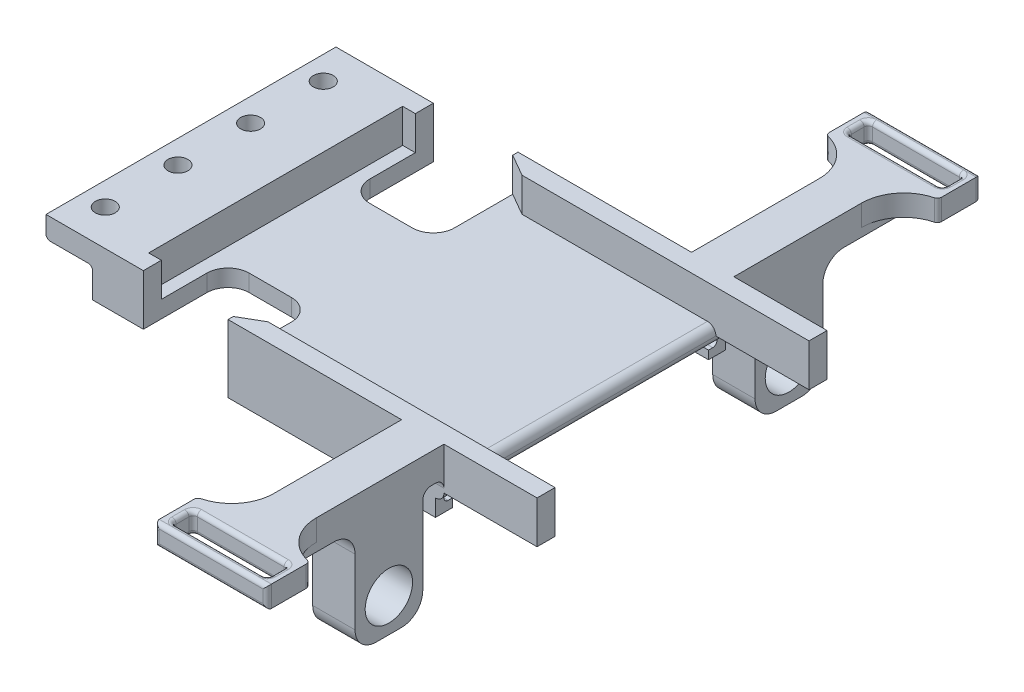
SolidWorks part; units mm, degrees
ref_plane "Front Plane" through (0, 0, 0) normal (0, 0, 1) x (1, 0, 0)
ref_plane "Top Plane" through (0, 0, 0) normal (0, 1, 0) x (1, 0, 0)
ref_plane "Right Plane" through (0, 0, 0) normal (1, 0, 0) x (0, 0, -1)
sketch "Sketch1" plane through (0, 0, 0) normal (0, 1, 0) x (1, 0, 0)
  line L1 (-62.4681, 12.4877) -> (31.5319, 12.4877)
  line L2 (-62.4681, 12.4877) -> (-62.4681, -56.0123)
  line L3 (-62.4681, -56.0123) -> (31.5319, -56.0123)
  line L4 (31.5319, 12.4877) -> (31.5319, -56.0123)
  dimension "D1" = 94
  dimension "D2" = 68.5
extrude "Boss-Extrude1" add sketch "Sketch1" along normal blind 12
sketch "Sketch3" plane through (0, 0, 56.0123) normal (0, 0, 1) x (1, 0, 0)
  line L0 (-62.4681, 12) -> (-62.4681, 0) construction
  line L1 (-62.4681, -3) -> (-51.4681, -3)
  line L2 (-62.4681, -3) -> (-62.4681, 7)
  line L3 (-62.4681, 7) -> (-51.4681, 7)
  line L4 (-51.4681, -3) -> (-51.4681, 7)
  line L5 (-62.4681, 12) -> (31.5319, 12) construction
  dimension "D1" = 11
  dimension "D2" = 10
  dimension "D3" = 5
extrude "Cut-Extrude1" cut sketch "Sketch3" against normal up to next
sketch "Sketch4" plane through (31.5319, 0, 0) normal (1, 0, 0) x (0, 0, -1)
  line L0 (-56.0123, 12) -> (12.4877, 12) construction
  line L1 (-51.7623, 12) -> (8.2377, 12)
  line L2 (-51.7623, 12) -> (-51.7623, 4)
  line L3 (-51.7623, 4) -> (8.2377, 4)
  line L4 (8.2377, 12) -> (8.2377, 4)
  line L5 (-56.0123, 12) -> (-56.0123, 0) construction
  dimension "D1" = 8
  dimension "D2" = 4.25
  dimension "D3" = 60
extrude "Cut-Extrude2" cut sketch "Sketch4" against normal blind 74
sketch "Sketch5" plane through (0, 7, 0) normal (0, -1, 0) x (1, 0, 0)
  line L0 (-56.9681, 56.0123) -> (-56.9681, -14.253) construction
  line L1 (-51.4681, 56.0123) -> (-62.4681, 56.0123) construction
  line L2 (-62.4681, -12.4877) -> (-51.4681, -12.4877) construction
  circle A0 centre (-56.9681, 47.5123) radius 2.35
  circle A1 centre (-56.9681, 30.3456) radius 2.35
  circle A2 centre (-56.9681, 13.179) radius 2.35
  circle A3 centre (-56.9681, -3.9877) radius 2.35
  dimension "D1" = 4.7
  dimension "D4" = 8.5
  dimension "D2" = 8.5
  dimension "D3" = 4
extrude "Cut-Extrude3" cut sketch "Sketch5" against normal up to next
ref_plane "Plane1" through (0, 0, 21.7623) normal (0, 0, 1) x (1, 0, 0)
sketch "Sketch9" plane through (0, 0, 56.0123) normal (0, 0, 1) x (1, 0, 0)
  line L1 (31.5319, 12) -> (21.5319, 12)
  line L2 (31.5319, 12) -> (31.5319, 5)
  line L3 (31.5319, 5) -> (21.5319, 5)
  line L4 (21.5319, 12) -> (21.5319, 5)
  line L5 (-62.4681, 12) -> (31.5319, 12) construction
  line L7 (31.5319, 12) -> (31.5319, 0) construction
  dimension "D1" = 7
  dimension "D2" = 10
extrude "Boss-Extrude2" add sketch "Sketch9" along normal blind 40
sketch "Sketch10" plane through (0, 5, 0) normal (0, -1, 0) x (1, 0, 0)
  line L0 (31.5319, 96.0123) -> (31.5319, 56.0123) construction
  line L1 (31.5319, 61.0123) -> (21.5319, 61.0123)
  line L2 (31.5319, 61.0123) -> (31.5319, 77.0123)
  line L3 (31.5319, 77.0123) -> (21.5319, 77.0123)
  line L4 (21.5319, 61.0123) -> (21.5319, 77.0123)
  line L5 (21.5319, 56.0123) -> (31.5319, 56.0123) construction
  dimension "D1" = 5
  dimension "D2" = 10
  dimension "D3" = 16
extrude "Boss-Extrude3" add sketch "Sketch10" along normal blind 25.5
sketch "Sketch11" plane through (31.5319, 0, 0) normal (1, 0, 0) x (0, 0, -1)
  line L0 (-61.0123, -20.5) -> (-61.0123, 5) construction
  line L1 (-61.0123, -20.5) -> (-77.0123, -20.5) construction
  circle A0 centre (-69.0123, -12.5) radius 5.6
  dimension "D1" = 11.2
  dimension "D2" = 8
  dimension "D3" = 8
extrude "Cut-Extrude6" cut sketch "Sketch11" against normal up to next
fillet "Fillet1" radius 5 3 edges at (26.5319, -20.5, 77.0123) (26.5319, -20.5, 61.0123) (26.5319, 5, 77.0123)
mirror "Mirror2" about plane through (0, 0, 21.7623) normal (0, 0, 1) of "Cut-Extrude6", "Boss-Extrude2", "Boss-Extrude3", "Fillet1"
fillet "Fillet2" radius 2 4 edges at (26.5319, 5, -12.4877) (26.5319, 5, 56.0123) (26.5319, 5, 61.0123) (26.5319, 5, -17.4877)
fillet "Fillet3" radius 1 2 edges at (-51.4681, 7, 21.7623) (-62.4681, 7, 21.7623)
sketch "Sketch12" plane through (0, 12, 0) normal (0, 1, 0) x (1, 0, 0)
  line L1 (13.2819, -96.0123) -> (39.7819, -96.0123)
  line L2 (13.2819, -96.0123) -> (13.2819, -106.0123)
  line L3 (13.2819, -106.0123) -> (39.7819, -106.0123)
  line L4 (39.7819, -96.0123) -> (39.7819, -106.0123)
  line L5 (31.5319, -96.0123) -> (21.5319, -96.0123) construction
  line L7 (15.2819, -99.0123) -> (37.7819, -99.0123)
  line L8 (15.2819, -99.0123) -> (15.2819, -104.0123)
  line L9 (15.2819, -104.0123) -> (37.7819, -104.0123)
  line L10 (37.7819, -99.0123) -> (37.7819, -104.0123)
  point P6 (26.5319, -96.0123)
  point P7 (26.5319, -96.0123)
  point P12 (26.5319, -99.0123)
  dimension "D1" = 26.5
  dimension "D2" = 10
  dimension "D3" = 22.5
  dimension "D4" = 5
  dimension "D5" = 2
extrude "Boss-Extrude4" add sketch "Sketch12" against normal blind 5
fillet "Fillet4" radius 10 2 edges at (21.5319, 9.5, 96.0123) (31.5319, 9.5, 96.0123)
fillet "Fillet5" radius 1 18 edges at (26.5319, 7, 99.0123) (15.2819, 7, 101.5123) (37.7819, 7, 101.5123) (26.5319, 12, 99.0123) (26.5319, 7, 104.0123) (37.7819, 9.5, 104.0123) (37.7819, 9.5, 99.0123) (15.2819, 9.5, 104.0123) (13.2819, 9.5, 106.0123) (13.2819, 9.5, 96.0123) (26.5319, 7, 106.0123) (26.5319, 12, 106.0123) (39.7819, 9.5, 106.0123) (39.7819, 9.5, 96.0123) (37.7819, 12, 101.5123) (26.5319, 12, 104.0123) (15.2819, 12, 101.5123) (15.2819, 9.5, 99.0123)
mirror "Mirror4" about plane through (0, 0, 21.7623) normal (0, 0, 1) of "Boss-Extrude4"
fillet "Fillet6" radius 10 2 edges at (21.5319, 9.5, -52.4877) (31.5319, 9.5, -52.4877)
fillet "Fillet7" radius 1 18 edges at (26.5319, 7, -55.4877) (15.2819, 7, -57.9877) (37.7819, 7, -57.9877) (37.7819, 12, -57.9877) (26.5319, 12, -55.4877) (26.5319, 7, -60.4877) (13.2819, 9.5, -52.4877) (37.7819, 9.5, -55.4877) (37.7819, 9.5, -60.4877) (15.2819, 9.5, -60.4877) (15.2819, 9.5, -55.4877) (15.2819, 12, -57.9877) (13.2819, 9.5, -62.4877) (26.5319, 7, -62.4877) (26.5319, 12, -62.4877) (26.5319, 12, -60.4877) (39.7819, 9.5, -52.4877) (39.7819, 9.5, -62.4877)
sketch "Sketch13" plane through (0, 0, 56.0123) normal (0, 0, 1) x (1, 0, 0)
  line L0 (-62.4681, 12) -> (21.5319, 12) construction
  line L1 (-39.4681, 12) -> (-19.4681, 12)
  line L2 (-39.4681, 12) -> (-39.4681, 0)
  line L3 (-39.4681, 0) -> (-19.4681, 0)
  line L4 (-19.4681, 12) -> (-19.4681, 0)
  line L5 (-51.4681, 0) -> (31.5319, 0) construction
  line L6 (-51.4681, 0) -> (-51.4681, 6) construction
  dimension "D1" = 20
  dimension "D2" = 12
extrude "Cut-Extrude7" cut sketch "Sketch13" against normal blind 20
fillet "Fillet8" radius 5 2 edges at (-39.4681, 2, 36.0123) (-19.4681, 2, 36.0123)
mirror "Mirror6" about plane through (0, 0, 21.7623) normal (0, 0, 1) of "Cut-Extrude7", "Fillet8"
chamfer "Chamfer3" distance 3 angle 60 1 edges at (-19.4681, 8, 51.7623) first distance on face at (-19.4681, 5.3333, 49.5956)
chamfer "Chamfer4" distance 3 angle 60 1 edges at (-19.4681, 8, -8.2377) first distance on face at (-19.4681, 5.3333, -6.071)
fillet "Fillet9" radius 2 2 edges at (31.5319, 4, 21.7623) (31.5319, 0, 21.7623)
sketch "Sketch14" plane through (31.5319, 0, 0) normal (1, 0, 0) x (0, 0, -1)
  line L1 (-56.0123, 2) -> (-51.7623, 2)
  line L2 (-56.0123, 2) -> (-56.0123, 12)
  line L3 (-56.0123, 12) -> (-51.7623, 12)
  line L4 (-51.7623, 2) -> (-51.7623, 12)
extrude "Boss-Extrude5" add sketch "Sketch14" along normal blind 22
mirror "Mirror7" about plane through (0, 0, 21.7623) normal (0, 0, 1) of "Boss-Extrude5"
sketch "Sketch15" plane through (0, 0, 0) normal (0, -1, 0) x (1, 0, 0)
  line L0 (29.5319, -12.4877) -> (29.5319, 56.0123) construction
  line L1 (-19.4681, 56.0123) -> (29.5319, 56.0123)
  line L2 (-19.4681, 56.0123) -> (-19.4681, 54.0123)
  line L3 (-19.4681, 54.0123) -> (29.5319, 54.0123)
  line L4 (29.5319, 56.0123) -> (29.5319, 54.0123)
  dimension "D1" = 2
extrude "Boss-Extrude6" add sketch "Sketch15" along normal blind 4
sketch "Sketch16" plane through (0, 0, 54.0123) normal (0, 0, -1) x (-1, 0, 0)
  line L0 (-29.5319, -4) -> (-29.5319, 0) construction
  line L1 (19.4681, -4) -> (-29.5319, -4)
  line L2 (19.4681, -4) -> (19.4681, -2)
  line L3 (19.4681, -2) -> (-29.5319, -2)
  line L4 (-29.5319, -4) -> (-29.5319, -2)
  dimension "D1" = 2
extrude "Boss-Extrude7" add sketch "Sketch16" along normal blind 2
fillet "Fillet10" radius 1 1 edges at (5.0319, -2, 54.0123)
mirror "Mirror8" about plane through (0, 0, 21.7623) normal (0, 0, 1) of "Boss-Extrude6", "Boss-Extrude7", "Fillet10"
hole_wizard "CSK for M3 Flat Head Machine Screw3" positions "Sketch18" profile "Sketch19" countersink size "M3" standard "ANSI Metric" end condition up to next
sketch "Sketch18" plane through (0, 7, 0) normal (0, -1, 0) x (-1, 0, 0)
  point P0 (56.9681, 3.9877)
  point P3 (56.9681, -13.179)
  point P6 (56.9681, -30.3456)
  point P9 (56.9681, -47.5123)
sketch "Sketch19" plane through (-56.9681, 7, -3.9877) normal (1, 0, 0) x (0, 0, -1)
  line L0 (0, 0) -> (0, 5)
  line L1 (0, 5) -> (1.7, 5)
  line L2 (1.7, 5) -> (1.7, 1.45)
  line L3 (1.7, 1.45) -> (3.15, 0)
  line L5 (3.15, 0) -> (0, 0)
  line L6 (-1.7, 1.45) -> (-3.15, 0) construction
  line L11 (0, -6.35) -> (0, 107.95) construction
  dimension "Thru Hole Dia." = 3.4
  dimension "Thru Hole Depth" = 5
  dimension "Near C'Sink Dia." = 6.3
  dimension "Near C'Sink Angle" = 90
